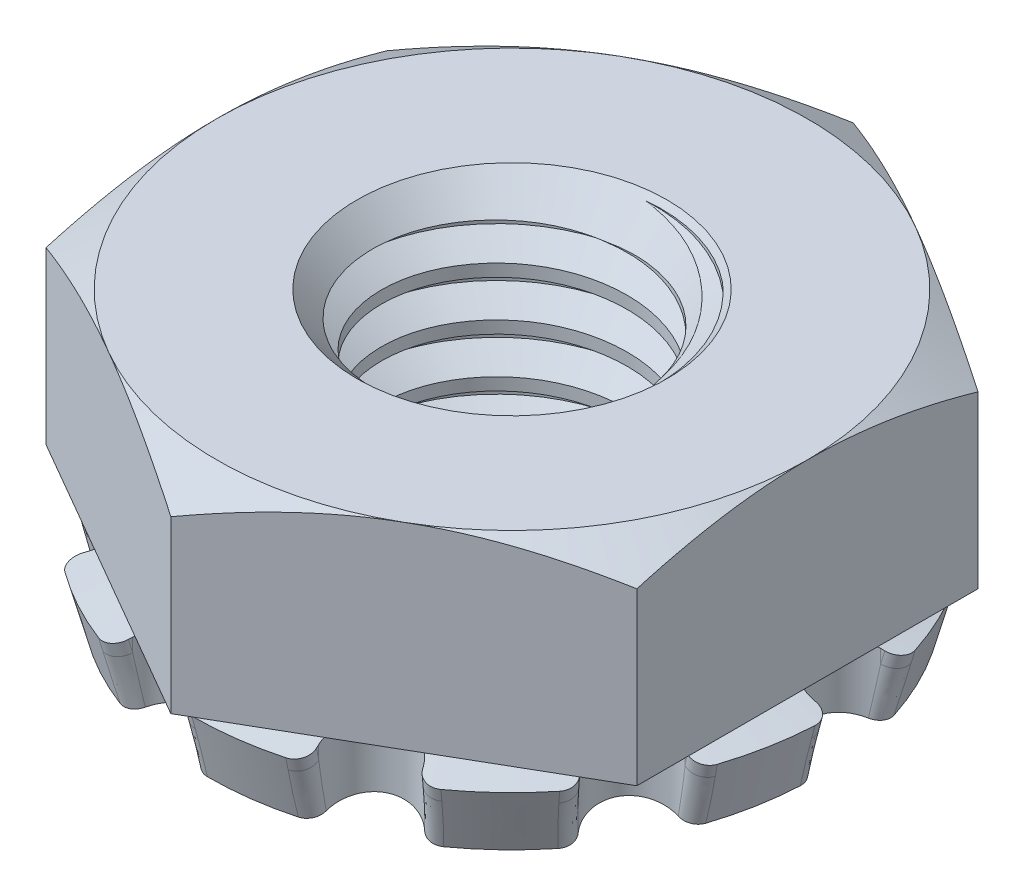
SolidWorks part; units mm, degrees
ref_plane "Front Plane" through (0, 0, 0) normal (0, 0, 1) x (1, 0, 0)
ref_plane "Top Plane" through (0, 0, 0) normal (0, 1, 0) x (1, 0, 0)
ref_plane "Right Plane" through (0, 0, 0) normal (1, 0, 0) x (0, 0, -1)
sketch "Sketch1" plane through (0, 0, 0) normal (0, 1, 0) x (1, 0, 0)
  line L1 (0, 5.4993) -> (-4.7625, 2.7496)
  line L2 (-4.7625, 2.7496) -> (-4.7625, -2.7496)
  line L3 (-4.7625, -2.7496) -> (0, -5.4993)
  line L4 (0, -5.4993) -> (4.7625, -2.7496)
  line L5 (4.7625, -2.7496) -> (4.7625, 2.7496)
  line L6 (4.7625, 2.7496) -> (0, 5.4993)
  circle A0 centre (0, 0) radius 4.7625 construction
  circle A1 centre (0, 0) radius 5.1594 construction
  point P9 (0, 5.4993)
  point P10 (0, 5.1594)
  dimension "Wd." = 9.525
  dimension "Washer Dia." = 10.3187
extrude "Boss-Extrude1" add sketch "Sketch1" along normal blind 4.3656
sketch "Sketch4" plane through (0, 4.3656, 0) normal (0, 1, 0) x (1, 0, 0)
  circle A0 centre (0, 0) radius 2.413
  dimension "Screw Dia." = 4.826
sketch "Sketch5" plane through (0, 4.3656, 0) normal (0, 1, 0) x (1, 0, 0)
  circle A1 centre (0, 0) radius 2.413
  circle A2 centre (0, 0) radius 2.413
  point P0 (0, 2.413)
  dimension "D1" = 0
curve "Helix/Spiral1" pitch 0.7937 height 5.1594 turns 6.5 parameters "Pitch"=0.7937
sketch "Sketch2" plane through (0, 4.3656, 0) normal (0, 1, 0) x (1, 0, 0)
  circle A0 centre (0, 0) radius 4.7625 construction
  circle A1 centre (0, 0) radius 4.7625
  point P3 (0, 4.7625)
extrude "Cut-Extrude1" cut sketch "Sketch2" against normal through all draft 60 flip side to cut
sketch "Sketch3" plane through (0, 0, 0) normal (0, -1, 0) x (1, 0, 0)
  circle A1 centre (0, 0) radius 4.7625
  circle A2 centre (0, 0) radius 4.7625
  dimension "D1" = 0
extrude "Cut-Extrude2" [suppressed] cut sketch "Sketch3" against normal through all draft 60 flip side to cut
extrude "Cut-Extrude3" cut sketch "Sketch4" against normal up to vertex (4.3656 mm away) up to point (0, 0, 0)
sketch "Sketch6" plane through (0, 0, 0) normal (1, 0, 0) x (0, 0, -1)
  line L0 (2.4989, 5.1098) -> (2.4989, 4.316) construction
  line L1 (2.4989, 4.316) -> (1.8115, 4.7129) construction
  line L2 (1.8115, 4.7129) -> (2.4989, 5.1098) construction
  line L3 (1.8974, 4.7625) -> (1.8974, 4.6633) construction
  line L4 (1.8115, 4.7129) -> (1.8974, 4.7129) construction
  line L5 (2.413, 5.0602) -> (2.413, 4.3656) construction
  line L6 (2.413, 4.7129) -> (2.4989, 4.7129) construction
  line L7 (2.456, 5.085) -> (1.9834, 4.8121)
  line L8 (1.9834, 4.8121) -> (1.9834, 4.6137)
  line L9 (1.9834, 4.6137) -> (2.456, 4.3408)
  line L10 (2.456, 4.3408) -> (2.456, 5.085)
  line L11 (1.8974, 4.7129) -> (1.9834, 4.7129) construction
  point P13 (2.456, 4.7129)
  dimension "D1" = 0.7937
  dimension "D2" = 0.0992
sweep "Sweep1" add profiles "Sketch6" path "Helix/Spiral1"
sketch "Sketch7" plane through (0, 4.3656, 0) normal (0, 1, 0) x (1, 0, 0)
  line L0 (-2.4989, 0) -> (0, 0) construction
  circle A0 centre (0, 0) radius 2.4989
extrude "Cut-Extrude4" cut sketch "Sketch7" against normal through all draft 45 and the other way through all draft 45
sketch "Sketch8" plane through (0, 0, 0) normal (0, -1, 0) x (1, 0, 0)
  circle A1 centre (0, 0) radius 2.4989
  circle A2 centre (0, 0) radius 2.4989
  dimension "D1" = 0
extrude "Cut-Extrude5" cut sketch "Sketch8" against normal through all draft 45 and the other way through all draft 45
sketch "Sketch9" plane through (0, 0, 0) normal (1, 0, 0) x (0, 0, -1)
  line L0 (5.1594, 0) -> (-5.1594, 0) construction
  line L1 (3.6036, 0) -> (5.4993, 0)
  line L2 (0, 0) -> (0, 1.1906) construction
  line L3 (3.6036, 1.1906) -> (5.4993, 1.1906)
  line L4 (5.4993, 0) -> (5.4993, 1.1906)
  line L5 (0, 1.1906) -> (0, 4.3656) construction
  line L6 (3.6036, 1.1906) -> (3.6036, 0)
  line L7 (2.413, 4.3656) -> (2.413, 1.1906) construction
  line L8 (2.413, 1.1906) -> (3.6036, 1.1906) construction
  dimension "D" = 3.175
revolve "Cut-Revolve1" cut sketch "Sketch9" angle 360 mid plane about L2
sketch "Sketch10" plane through (0, 0, 0) normal (1, 0, 0) x (0, 0, -1)
  line L0 (3.6036, 1.1906) -> (3.6036, 0) construction
  line L1 (3.6036, 1.1906) -> (4.395, 1.1906)
  line L2 (3.6036, 1.1906) -> (3.6036, 0.2048)
  line L3 (3.6036, 0.2048) -> (4.1308, 0.2048)
  line L4 (5.1594, 0.9858) -> (4.8952, 0)
  line L5 (0, 1.1906) -> (0, 0) construction
  line L6 (5.1594, 0.9858) -> (4.395, 1.1906)
  line L7 (4.8952, 0) -> (4.1308, 0.2048)
  line L8 (4.1308, 0.2048) -> (4.395, 1.1906) construction
  line L9 (3.6036, 0) -> (5.4993, 0) construction
  dimension "D1" = 165
revolve "Revolve1" add sketch "Sketch10" angle 360 mid plane about L5
sketch "Sketch11" plane through (0, 0, 0) normal (0, 1, 0) x (1, 0, 0)
  line L0 (0, 0) -> (5.1594, 0) construction
  line L1 (0, 0) -> (4.9836, 1.3353) construction
  line L2 (4.688, 1.2561) -> (4.9836, 1.3353)
  line L3 (4.8533, 0) -> (5.1594, 0)
  circle A0 centre (0, 0) radius 5.1594 construction
  arc A1 (4.688, 1.2561) -> (4.8533, 0) centre (4.8533, 0.639) ccw
  arc A2 (5.1594, 0) -> (4.9836, 1.3353) centre (0, 0) ccw
  circle A3 centre (0, 0) radius 4.8952 construction
  dimension "D1" = 15
extrude "Cut-Extrude6" cut sketch "Sketch11" along normal up to vertex (1.1906 mm away) up to point (0, 1.1906, 0)
fillet "Fillet1" radius 0.254 2 edges at (4.856, 0.4929, -1.3012) (5.0273, 0.4929, 0)
pattern_circular "CirPattern1" count 10 over 360 about axis through (0, 0, 0) along (0, -1, 0) of "Cut-Extrude6", "Fillet1"
equation "\"D3@Helix/Spiral1\" = \"Pitch@Helix/Spiral1\" + \"Ht.@Boss-Extrude1\""
equation "\"D1@Sketch6\" = \"Pitch@Helix/Spiral1\""
equation "\"D2@Sketch6\" = \"D1@Sketch6\" / 8"
